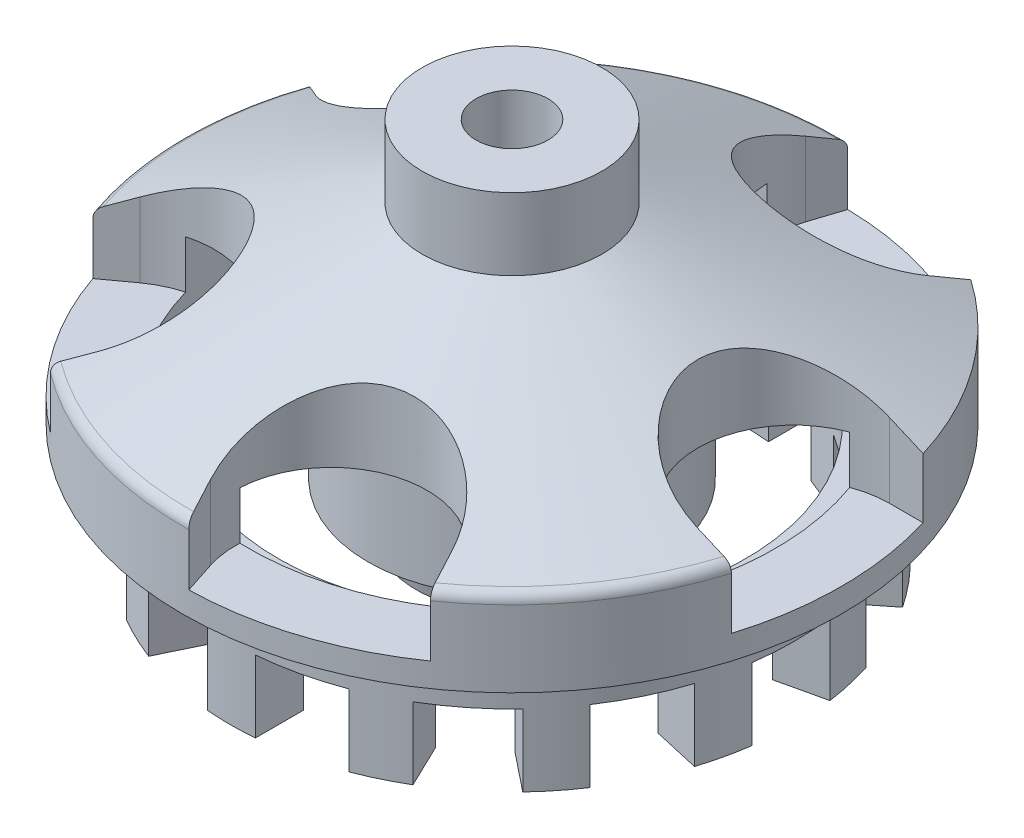
SolidWorks part; units mm, degrees
material "6061-T6 (SS)"
ref_plane "Front Plane" through (0, 0, 0) normal (0, 0, 1) x (1, 0, 0)
ref_plane "Top Plane" through (0, 0, 0) normal (0, 1, 0) x (1, 0, 0)
ref_plane "Right Plane" through (0, 0, 0) normal (1, 0, 0) x (0, 0, -1)
sketch "Sketch1" plane through (0, 0, 0) normal (0, 1, 0) x (1, 0, 0)
  circle A0 centre (0, 0) radius 13.75
  dimension "D1" = 27.5
extrude "Boss-Extrude1" add sketch "Sketch1" along normal blind 8
sketch "Sketch2" plane through (0, 0, 0) normal (1, 0, 0) x (0, 0, -1)
  line L0 (3.75, 8) -> (13.75, 3.5)
  line L1 (13.75, 8) -> (-13.75, 8) construction
  line L2 (13.75, 0) -> (13.75, 8) construction
  line L3 (13.75, 3.5) -> (13.75, 8)
  line L4 (13.75, 8) -> (3.75, 8)
  line L5 (55, 0) -> (-55, 0) construction
  line L6 (0, 0) -> (0, 8) construction
  line L7 (0, 55) -> (0, -55) construction
  dimension "D1" = 3.5
  dimension "D2" = 10
revolve "Cut-Revolve1" cut sketch "Sketch2" angle 360 about L6
sketch "Sketch3" plane through (0, 0, 0) normal (0, -1, 0) x (-1, 0, 0)
  circle A0 centre (0, 0) radius 9.75
  circle A1 centre (0, 0) radius 11.75
  dimension "D1" = 19.5
  dimension "D2" = 23.5
extrude "Boss-Extrude2" add sketch "Sketch3" along normal blind 5
sketch "Sketch4" plane through (0, -5, 0) normal (0, -1, 0) x (-1, 0, 0)
  line L0 (0, 0) -> (-3.0597, -13.4053) construction
  line L1 (0, 0) -> (-5.9659, -12.3883) construction
  line L2 (0, 4.4) -> (0, -4.4) construction
  line L3 (-1, -11.7074) -> (-1, -9.6986)
  line L4 (-4.1787, -10.9819) -> (-3.3071, -9.172)
  line L5 (-8.5297, -8.0813) -> (-6.9592, -6.8288)
  line L6 (-5.9806, -10.1141) -> (-5.109, -8.3042)
  line L7 (-11.1913, -3.5801) -> (-9.2329, -3.1331)
  line L8 (-9.7767, -6.5176) -> (-8.2061, -5.2651)
  line L9 (-11.6364, 1.6302) -> (-9.6779, 1.1832)
  line L10 (-11.6364, -1.6302) -> (-9.6779, -1.1832)
  line L11 (-9.7767, 6.5176) -> (-8.2061, 5.2651)
  line L12 (-11.1913, 3.5801) -> (-9.2329, 3.1331)
  line L13 (-5.9806, 10.1141) -> (-5.109, 8.3042)
  line L14 (-8.5297, 8.0813) -> (-6.9592, 6.8288)
  line L15 (-1, 11.7074) -> (-1, 9.6986)
  line L16 (-4.1787, 10.9819) -> (-3.3071, 9.172)
  line L17 (4.1787, 10.9819) -> (3.3071, 9.172)
  line L18 (1, 11.7074) -> (1, 9.6986)
  line L19 (8.5297, 8.0813) -> (6.9592, 6.8288)
  line L20 (5.9806, 10.1141) -> (5.109, 8.3042)
  line L21 (11.1913, 3.5801) -> (9.2329, 3.1331)
  line L22 (9.7767, 6.5176) -> (8.2061, 5.2651)
  line L23 (11.6364, -1.6302) -> (9.6779, -1.1832)
  line L24 (11.6364, 1.6302) -> (9.6779, 1.1832)
  line L25 (9.7767, -6.5176) -> (8.2061, -5.2651)
  line L26 (11.1913, -3.5801) -> (9.2329, -3.1331)
  line L27 (5.9806, -10.1141) -> (5.109, -8.3042)
  line L28 (8.5297, -8.0813) -> (6.9592, -6.8288)
  line L29 (1, -11.7074) -> (1, -9.6986)
  line L30 (4.1787, -10.9819) -> (3.3071, -9.172)
  circle A0 centre (0, 0) radius 13.75 construction
  arc A1 (-1, -11.7074) -> (-4.1787, -10.9819) centre (0, 0) cw
  circle A2 centre (0, 0) radius 11.75 construction
  circle A3 centre (0, 0) radius 9.75 construction
  arc A4 (-1, -9.6986) -> (-3.3071, -9.172) centre (0, 0) cw
  arc A5 (-5.109, -8.3042) -> (-6.9592, -6.8288) centre (0, 0) cw
  arc A6 (-5.9806, -10.1141) -> (-8.5297, -8.0813) centre (0, 0) cw
  arc A7 (-8.2061, -5.2651) -> (-9.2329, -3.1331) centre (0, 0) cw
  arc A8 (-9.7767, -6.5176) -> (-11.1913, -3.5801) centre (0, 0) cw
  arc A9 (-9.6779, -1.1832) -> (-9.6779, 1.1832) centre (0, 0) cw
  arc A10 (-11.6364, -1.6302) -> (-11.6364, 1.6302) centre (0, 0) cw
  arc A11 (-9.2329, 3.1331) -> (-8.2061, 5.2651) centre (0, 0) cw
  arc A12 (-11.1913, 3.5801) -> (-9.7767, 6.5176) centre (0, 0) cw
  arc A13 (-6.9592, 6.8288) -> (-5.109, 8.3042) centre (0, 0) cw
  arc A14 (-8.5297, 8.0813) -> (-5.9806, 10.1141) centre (0, 0) cw
  arc A15 (-3.3071, 9.172) -> (-1, 9.6986) centre (0, 0) cw
  arc A16 (-4.1787, 10.9819) -> (-1, 11.7074) centre (0, 0) cw
  arc A17 (1, 9.6986) -> (3.3071, 9.172) centre (0, 0) cw
  arc A18 (1, 11.7074) -> (4.1787, 10.9819) centre (0, 0) cw
  arc A19 (5.109, 8.3042) -> (6.9592, 6.8288) centre (0, 0) cw
  arc A20 (5.9806, 10.1141) -> (8.5297, 8.0813) centre (0, 0) cw
  arc A21 (8.2061, 5.2651) -> (9.2329, 3.1331) centre (0, 0) cw
  arc A22 (9.7767, 6.5176) -> (11.1913, 3.5801) centre (0, 0) cw
  arc A23 (9.6779, 1.1832) -> (9.6779, -1.1832) centre (0, 0) cw
  arc A24 (11.6364, 1.6302) -> (11.6364, -1.6302) centre (0, 0) cw
  arc A25 (9.2329, -3.1331) -> (8.2061, -5.2651) centre (0, 0) cw
  arc A26 (11.1913, -3.5801) -> (9.7767, -6.5176) centre (0, 0) cw
  arc A27 (6.9592, -6.8288) -> (5.109, -8.3042) centre (0, 0) cw
  arc A28 (8.5297, -8.0813) -> (5.9806, -10.1141) centre (0, 0) cw
  arc A29 (3.3071, -9.172) -> (1, -9.6986) centre (0, 0) cw
  arc A30 (4.1787, -10.9819) -> (1, -11.7074) centre (0, 0) cw
  point P71 (0, 0)
  dimension "D1" = 25.714
  dimension "D2" = 12.857
  dimension "D3" = 1
  dimension "D4" = 14
extrude "Cut-Extrude1" cut sketch "Sketch4" against normal blind 3
sketch "Sketch5" plane through (0, 8, 0) normal (0, 1, 0) x (1, 0, 0)
  line L0 (45.2306, 0) -> (11.75, 0) construction
  line L1 (-7.15, 0) -> (7.15, 0) construction
  line L2 (45.2306, -4) -> (11.75, -4)
  line L3 (45.2306, 4) -> (11.75, 4)
  arc A0 (45.2306, -4) -> (45.2306, 4) centre (45.2306, 0) ccw
  arc A1 (11.75, 4) -> (11.75, -4) centre (11.75, 0) ccw
  circle A3 centre (0, 0) radius 13.75 construction
  point P5 (28.4903, 0)
  dimension "D1" = 4
  dimension "D2" = 6
extrude "Cut-Extrude2" cut sketch "Sketch5" against normal blind 7
pattern_circular "CirPattern1" count 5 over 360 about axis through (0, 0, 0) along (0, 1, 0) of "Cut-Extrude2"
sketch "Sketch6" plane through (0, 0, 0) normal (0, 0, 1) x (1, 0, 0)
  line L0 (0, 3) -> (0, 0)
  line L1 (0, -7.15) -> (0, 7.15) construction
  line L2 (0, 0) -> (11, 0)
  line L3 (15.125, 0) -> (-15.125, 0) construction
  line L4 (11, 0) -> (11, 3)
  line L5 (11, 3) -> (0, 3)
  line L6 (3.75, 8) -> (-3.75, 8) construction
  line L7 (0, 0) -> (0, 8.019) construction
  dimension "D1" = 5
  dimension "D2" = 11
revolve "Cut-Revolve2" cut sketch "Sketch6" angle 360 about L7
sketch "Sketch7" plane through (0, 8, 0) normal (0, 1, 0) x (1, 0, 0)
  circle A0 centre (0, 0) radius 3.75
  dimension "D1" = 7.5
extrude "Boss-Extrude3" add sketch "Sketch7" along normal blind 3
sketch "Sketch11" plane through (0, 3, 0) normal (0, -1, 0) x (-1, 0, 0)
  circle A0 centre (0, 0) radius 6
extrude "Boss-Extrude4" add sketch "Sketch11" along normal blind 5
sketch "Sketch12" plane through (0, 11, 0) normal (0, 1, 0) x (1, 0, 0)
  circle A0 centre (0, 0) radius 1.5
  dimension "D1" = 3
extrude "Cut-Extrude3" cut sketch "Sketch12" against normal up to surface (13 mm away) up to face at (0, -2, -6)
sketch "Sketch13" plane through (0, -2, 0) normal (0, -1, 0) x (-1, 0, 0)
  circle A0 centre (0, 0) radius 3
  circle A1 centre (0, 0) radius 4
extrude "Boss-Extrude5" add sketch "Sketch13" along normal blind 2
chamfer "Chamfer1" distance 0.5 distance2 2 1 edges at (0, -2, -4)
ref_plane "Plane1" through (7.75, 0, 0) normal (1, 0, 0) x (0, 0, -1)
ref_plane "Plane2" through (9.75, 0, 0) normal (1, 0, 0) x (0, 0, -1)
fillet "Fillet1" radius 0.5 4 edges at (-4.249, 3.5, 13.077) (-13.75, 3.5, 0) (-4.249, 3.5, -13.077) (11.124, 3.5, 8.082)
equation "\"D1@Sketch3\"=\"D2@Sketch3\"-4"
